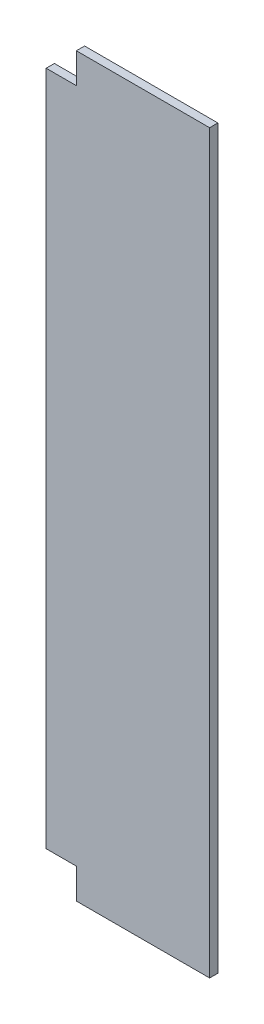
SolidWorks part; units mm, degrees
ref_plane "Front Plane" through (0, 0, 0) normal (0, 0, 1) x (1, 0, 0)
ref_plane "Top Plane" through (0, 0, 0) normal (0, 1, 0) x (1, 0, 0)
ref_plane "Right Plane" through (0, 0, 0) normal (1, 0, 0) x (0, 0, -1)
sketch "Sketch1" plane through (0, 0, 0) normal (0, 0, 1) x (1, 0, 0)
  line L0 (-107.5693, -326.8557) -> (-107.5693, -304.8557)
  line L1 (-107.5693, 209.1443) -> (-10.5693, 209.1443)
  line L2 (-129.5693, 187.1443) -> (-129.5693, -304.8557)
  line L3 (-107.5693, -326.8557) -> (-10.5693, -326.8557)
  line L4 (-10.5693, 209.1443) -> (-10.5693, -326.8557)
  line L5 (-107.5693, -304.8557) -> (-129.5693, -304.8557)
  line L6 (-129.5693, 187.1443) -> (-107.5693, 187.1443)
  line L7 (-107.5693, 187.1443) -> (-107.5693, 209.1443)
  dimension "D1" = 536
  dimension "D2" = 119
  dimension "D3" = 22
extrude "Boss-Extrude1" add sketch "Sketch1" along normal blind 6 contours L1 L4 L3 L0 L5 L2 L6 L7
